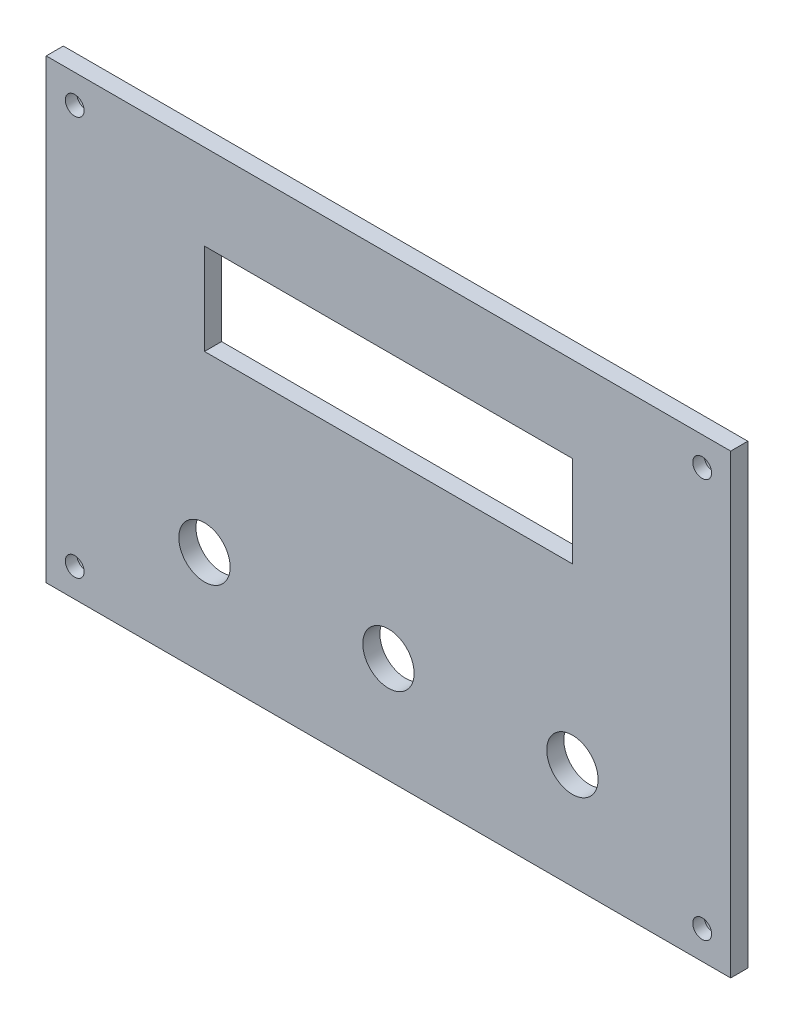
SolidWorks part; units mm, degrees
ref_plane "Přední rovina" through (0, 0, 0) normal (0, 0, 1) x (1, 0, 0)
ref_plane "Horní rovina" through (0, 0, 0) normal (0, 1, 0) x (1, 0, 0)
ref_plane "Pravá rovina" through (0, 0, 0) normal (1, 0, 0) x (0, 0, -1)
sketch "Skica1" plane through (0, 0, 0) normal (0, 0, 1) x (1, 0, 0)
  line L1 (-60, 40) -> (60, 40)
  line L2 (-60, 40) -> (-60, -40)
  line L3 (-60, -40) -> (60, -40)
  line L4 (60, 40) -> (60, -40)
  line L5 (-60, 40) -> (60, -40) construction
  line L6 (-60, -40) -> (60, 40) construction
  line L7 (-32.25, 25) -> (32.25, 25)
  line L8 (-32.25, 25) -> (-32.25, 9)
  line L9 (-32.25, 9) -> (32.25, 9)
  line L10 (32.25, 25) -> (32.25, 9)
  line L11 (-32.25, 25) -> (32.25, 9) construction
  line L12 (-32.25, 9) -> (32.25, 25) construction
  circle A0 centre (-32.25, -21.5) radius 4.5
  circle A1 centre (0, -21.5) radius 4.5
  circle A2 centre (32.25, -21.5) radius 4.5
  point P0 (0, 0)
  point P6 (0, 17)
  point P17 (0, 0)
  point P18 (0, 0)
  point P19 (0, 0)
  point P20 (0, 0)
  point P21 (0, 0)
  dimension "D8" = 9
  dimension "D9" = 9
  dimension "D10" = 9
  dimension "D1" = 120
  dimension "D2" = 80
  dimension "D3" = 15
  dimension "D4" = 64.5
  dimension "D5" = 16
  dimension "D6" = 27.75
  dimension "D7" = 27.75
extrude "Přidat vysunutím3" add sketch "Skica1" along normal blind 3 contours L1 L4 L3 L2
extrude "Odebrat vysunutím1" cut sketch "Skica1<4>" along normal blind 3 flip side to cut
sketch "Skica1<4>" plane through (0, 0, 0) normal (0, 0, 1) x (1, 0, 0) same geometry as "Skica1"
sketch "Skica5" plane through (0, 0, 3) normal (0, 0, 1) x (1, 0, 0)
  line L0 (60, 40) -> (60, -40) construction
  line L1 (-60, 40) -> (60, 40) construction
  line L2 (-60, 40) -> (-60, -40) construction
  line L3 (-60, -40) -> (60, -40) construction
  circle A0 centre (-55, 35) radius 1.65
  circle A1 centre (55, 35) radius 1.65
  circle A2 centre (-55, -35) radius 1.65
  circle A3 centre (55, -35) radius 1.65
  point P16 (0, 0)
  dimension "D1" = 3.3
  dimension "D2" = 5
  dimension "D3" = 5
  dimension "D4" = 5
  dimension "D5" = 5
  dimension "D6" = 3.3
  dimension "D7" = 5
  dimension "D8" = 5
  dimension "D9" = 3.3
  dimension "D10" = 5
  dimension "D11" = 5
  dimension "D12" = 3.3
extrude "Odebrat vysunutím3" cut sketch "Skica5" against normal blind 2 contours A0 | A1 | A3 | A2
sketch "Skica6" plane through (0, 0, 1) normal (0, 0, 1) x (1, 0, 0)
  circle A0 centre (-55, 35) radius 2.5
  circle A1 centre (55, 35) radius 2.5
  circle A2 centre (55, -35) radius 2.5
  circle A3 centre (-55, -35) radius 2.5
  dimension "D1" = 5
  dimension "D2" = 5
  dimension "D3" = 5
  dimension "D4" = 5
extrude "Odebrat vysunutím6" cut sketch "Skica6" against normal blind 1 contours A1 | A0 | A3 | A2
